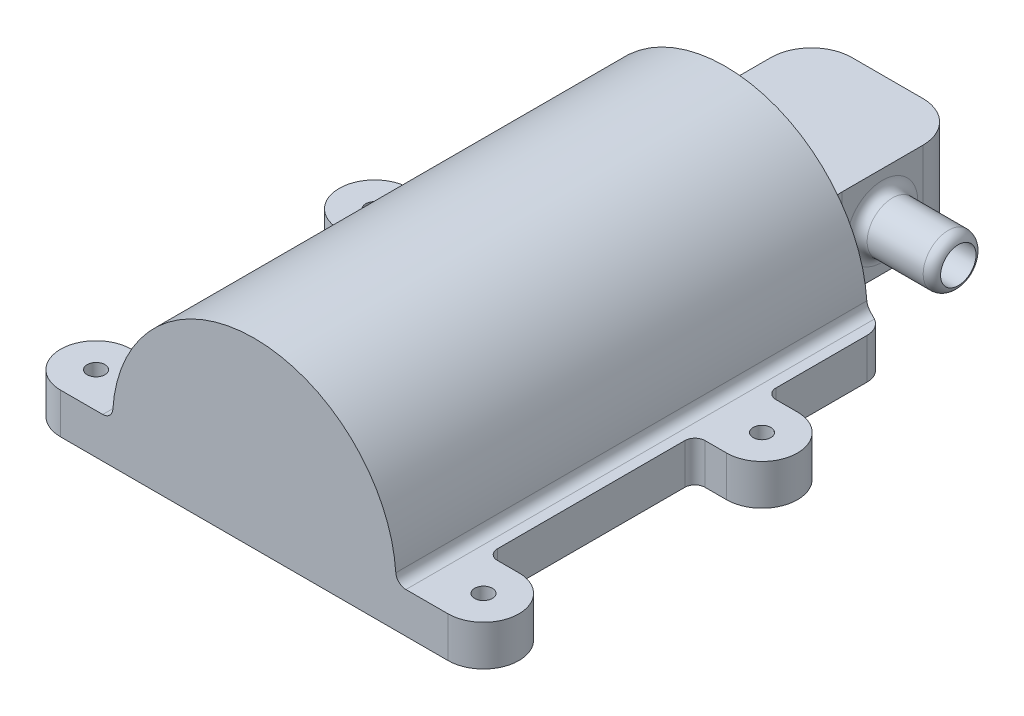
SolidWorks part; units mm, degrees
ref_plane "前视基准面" through (0, 0, 0) normal (0, 0, 1) x (1, 0, 0)
ref_plane "上视基准面" through (0, 0, 0) normal (0, 1, 0) x (1, 0, 0)
ref_plane "右视基准面" through (0, 0, 0) normal (1, 0, 0) x (0, 0, -1)
other "Configuration Table"
sketch "草图1" plane through (0, 0, 0) normal (0, 1, 0) x (1, 0, 0)
  line L0 (0, 49.8731) -> (0, -34.845) construction
  line L1 (0, 0) -> (-73.4019, 0) construction
  line L2 (-38.25, 34.5) -> (-34, 34.5)
  line L3 (-38.25, -34.5) -> (38.25, -34.5)
  line L4 (-32, 36.5) -> (-32, 54.5)
  line L5 (-28, 58.5) -> (-23, 58.5)
  line L6 (-15, 66.5) -> (-15, 82.5)
  line L7 (-7, 90.5) -> (7, 90.5)
  line L8 (15, 66.5) -> (15, 82.5)
  line L9 (28, 58.5) -> (23, 58.5)
  line L10 (32, 36.5) -> (32, 54.5)
  line L11 (38.25, 34.5) -> (34, 34.5)
  line L12 (-38.25, 20.5) -> (-34, 20.5)
  line L13 (-32, 18.5) -> (-32, -18.5)
  line L14 (38.25, 20.5) -> (34, 20.5)
  line L15 (32, 18.5) -> (32, -18.5)
  line L16 (38.25, -20.5) -> (34, -20.5)
  line L17 (-38.25, -20.5) -> (-34, -20.5)
  line L18 (-32, 18.5) -> (-32, 36.5)
  line L19 (32, 18.5) -> (32, 36.5)
  line L20 (-32, -18.5) -> (-32, -34.5)
  line L21 (32, -18.5) -> (32, -34.5)
  arc A0 (-38.25, 34.5) -> (-38.25, 20.5) centre (-38.25, 27.5) ccw
  arc A1 (38.25, 34.5) -> (38.25, 20.5) centre (38.25, 27.5) cw
  arc A2 (38.25, -34.5) -> (38.25, -20.5) centre (38.25, -27.5) ccw
  arc A3 (-38.25, -34.5) -> (-38.25, -20.5) centre (-38.25, -27.5) cw
  arc A4 (-34, 34.5) -> (-32, 36.5) centre (-34, 36.5) ccw
  arc A5 (-32, 54.5) -> (-28, 58.5) centre (-28, 54.5) cw
  arc A6 (-15, 82.5) -> (-7, 90.5) centre (-7, 82.5) cw
  arc A7 (-23, 58.5) -> (-15, 66.5) centre (-23, 66.5) ccw
  arc A8 (15, 82.5) -> (7, 90.5) centre (7, 82.5) ccw
  arc A9 (23, 58.5) -> (15, 66.5) centre (23, 66.5) cw
  arc A10 (32, 54.5) -> (28, 58.5) centre (28, 54.5) ccw
  arc A11 (34, 34.5) -> (32, 36.5) centre (34, 36.5) cw
  arc A12 (-34, 20.5) -> (-32, 18.5) centre (-34, 18.5) cw
  arc A13 (34, 20.5) -> (32, 18.5) centre (34, 18.5) ccw
  arc A14 (34, -20.5) -> (32, -18.5) centre (34, -18.5) cw
  arc A15 (-34, -20.5) -> (-32, -18.5) centre (-34, -18.5) ccw
  point P24 (-32, 34.5)
  point P27 (-32, 58.5)
  point P30 (-15, 90.5)
  point P33 (-15, 58.5)
  point P35 (0, 90.5)
  point P57 (32, 0)
  point P58 (-32, 0)
  dimension "D1" = 7
  dimension "D10" = 2
  dimension "D11" = 4
  dimension "D12" = 8
  dimension "D13" = 2
  dimension "D2" = 38.25
  dimension "D3" = 27.5
  dimension "D4" = 125
  dimension "D5" = 24
  dimension "D6" = 17
  dimension "D7" = 32
  dimension "D8" = 15
  dimension "D9" = 6.25
  dimension "D14" = 64
extrude "凸台-拉伸1" add sketch "草图1" along normal blind 8 contours L12 A12 L18 A4 L2 A0 | A15 L17 A3 L3 L20 | L16 A14 L21 L3 A2 | A13 L14 A1 L11 A11 L19 | L16 A14 L15 A13 L14 A1 L11 A11 L10 A10 L9 A9 L8 A8 L7 A6 L6 A7 L5 A5 L4 A4 L2 A0 L12 A12 L13 A15 L17 A3 L3 A2 region at (-37.9206, 0, -27.5) region at (-37.9491, 0, 27.4613) region at (37.9491, 0, 27.4613) region at (37.9206, 0, -27.5)
sketch "草图3" plane through (0, 8, 0) normal (0, 1, 0) x (1, 0, 0)
  circle A0 centre (-38.25, 27.5) radius 1.75
  circle A1 centre (38.25, 27.5) radius 1.75
  circle A2 centre (-38.25, -27.5) radius 1.75
  circle A3 centre (38.25, -27.5) radius 1.75
  dimension "D1" = 3.5
extrude "切除-拉伸1" cut sketch "草图3" against normal up to next
sketch "草图6" plane through (0, 0, 34.5) normal (0, 0, 1) x (1, 0, 0)
  line L0 (-38.25, 8) -> (38.25, 8) construction
  line L1 (-28, 8) -> (28, 8)
  arc A0 (-28, 8) -> (28, 8) centre (0, 8) cw
  dimension "D1" = 56
extrude "凸台-拉伸3" add sketch "草图6" against normal blind 93
sketch "草图7" plane through (0, 8, 0) normal (0, 1, 0) x (1, 0, 0)
  line L0 (23, 58.5) -> (-23, 58.5)
  line L1 (-15, 66.5) -> (-15, 82.5)
  line L2 (-7, 90.5) -> (7, 90.5)
  line L3 (15, 82.5) -> (15, 66.5)
  arc A0 (-23, 58.5) -> (-15, 66.5) centre (-23, 66.5) ccw
  arc A1 (-15, 82.5) -> (-7, 90.5) centre (-7, 82.5) cw
  arc A2 (7, 90.5) -> (15, 82.5) centre (7, 82.5) cw
  arc A3 (15, 66.5) -> (23, 58.5) centre (23, 66.5) ccw
extrude "凸台-拉伸4" add sketch "草图7" along normal blind 10
sketch "草图9" plane through (0, 0, 0) normal (1, 0, 0) x (0, 0, -1)
  line L0 (74.5, 18) -> (74.5, 0) construction
  line L1 (66.5, 18) -> (82.5, 18) construction
  line L2 (66.5, 0) -> (82.5, 0) construction
  circle A0 centre (74.5, 9) radius 5
  dimension "D1" = 10
extrude "凸台-拉伸6" add sketch "草图9" along normal mid plane 60
sketch "草图10" plane through (-30, 0, 0) normal (-1, 0, 0) x (0, 0, 1)
  circle A0 centre (-74.5, 9) radius 3.5
  dimension "D1" = 7
extrude "切除-拉伸2" cut sketch "草图10" against normal up to next
fillet "圆角1" radius 2 2 edges at (-30, 9, -79.5) (30, 9, -79.5)
fillet "圆角2" radius 2 3 edges at (28, 8, -12) (-28, 8, -12) (0, 18, -58.5)
ref_plane "基准面1" through (0, 0, 27.5) normal (0, 0, -1) x (-1, 0, 0)
sketch "草图12" plane through (0, 0, 27.5) normal (0, 0, 1) x (1, 0, 0)
  line L0 (0, 0) -> (0, 36) construction
  line L1 (-38.25, 0) -> (38.25, 0) construction
  line L2 (-5, 10) -> (5, 10)
  line L3 (-5, 10) -> (-5, 0)
  line L4 (-5, 0) -> (5, 0)
  line L5 (5, 10) -> (5, 0)
  line L6 (-5, 10) -> (5, 0) construction
  line L7 (-5, 0) -> (5, 10) construction
  arc A0 (27.9377, 9.8667) -> (-27.9377, 9.8667) centre (0, 8) ccw construction
  circle A1 centre (0, 5) radius 5
  circle A2 centre (0, 5) radius 3.5
  dimension "D1" = 10
  dimension "D3" = 7
  dimension "D2" = 10
extrude "切除-拉伸5" cut sketch "草图12" against normal up to next contours L3 A1 L4 | L4 A1 L5 | A2 region at (-3.8832, 1.1168, 27.5) region at (3.8832, 1.1168, 27.5)
fillet "圆角4" radius 2 2 edges at (-5, 0, -31.5) (5, 0, -31.5)
fillet "圆角5" radius 2 2 edges at (15, 9, -69.5) (-15, 9, -69.5)
